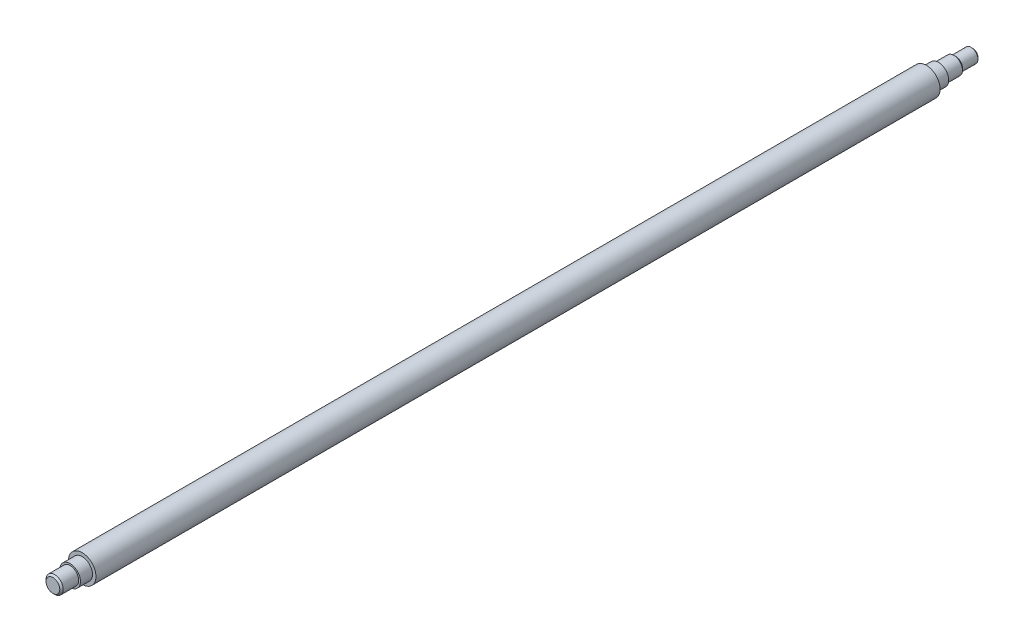
SolidWorks part; units mm, degrees
material "Ductile Iron (SN)"
ref_plane "Front Plane" through (0, 0, 0) normal (0, 0, 1) x (1, 0, 0)
ref_plane "Top Plane" through (0, 0, 0) normal (0, 1, 0) x (1, 0, 0)
ref_plane "Right Plane" through (0, 0, 0) normal (1, 0, 0) x (0, 0, -1)
sketch "Sketch1" plane through (0, 0, 0) normal (0, 0, 1) x (1, 0, 0)
  circle A0 centre (0, 0) radius 8
  dimension "D1" = 16
extrude "Boss-Extrude1" add sketch "Sketch1" along normal blind 490
sketch "Sketch4" plane through (0, 0, 0) normal (0, 0, 1) x (1, 0, 0)
  circle A0 centre (0, 0) radius 6
  dimension "D1" = 12
sketch "Sketch6" plane through (0, 0, 0) normal (0, 0, -1) x (-1, 0, 0)
  circle A0 centre (0, 0) radius 6
  dimension "D1" = 12
extrude "Boss-Extrude2" add sketch "Sketch6" along normal blind 5
sketch "Sketch7" plane through (0, 0, -5) normal (0, 0, -1) x (-1, 0, 0)
  circle A0 centre (0, 0) radius 6
  dimension "D1" = 12
extrude "Boss-Extrude3" add sketch "Sketch7" along normal blind 2
sketch "Sketch8" plane through (0, 0, -7) normal (0, 0, -1) x (-1, 0, 0)
  circle A0 centre (0, 0) radius 5
  dimension "D1" = 10
extrude "Boss-Extrude4" add sketch "Sketch8" along normal blind 10
sketch "Sketch9" plane through (0, 0, -17) normal (0, 0, -1) x (-1, 0, 0)
  circle A0 centre (0, 0) radius 4
  dimension "D1" = 8
extrude "Boss-Extrude5" add sketch "Sketch9" along normal blind 10
chamfer "Chamfer1" distance 1 angle 45 1 edges at (-5, 0, -17)
chamfer "Chamfer2" distance 1 angle 45 1 edges at (-4, 0, -27)
sketch "Sketch10" plane through (0, 0, 490) normal (0, 0, 1) x (1, 0, 0)
  circle A0 centre (0, 0) radius 6
  dimension "D1" = 12
extrude "Boss-Extrude6" add sketch "Sketch10" along normal blind 5
sketch "Sketch11" plane through (0, 0, 495) normal (0, 0, 1) x (1, 0, 0)
  circle A0 centre (0, 0) radius 6
  dimension "D1" = 12
extrude "Boss-Extrude7" add sketch "Sketch11" along normal blind 2
sketch "Sketch12" plane through (0, 0, 497) normal (0, 0, 1) x (1, 0, 0)
  circle A0 centre (0, 0) radius 5
  dimension "D1" = 10
extrude "Boss-Extrude8" add sketch "Sketch12" along normal blind 10
chamfer "Chamfer3" distance 1 angle 45 1 edges at (5, 0, 507)
